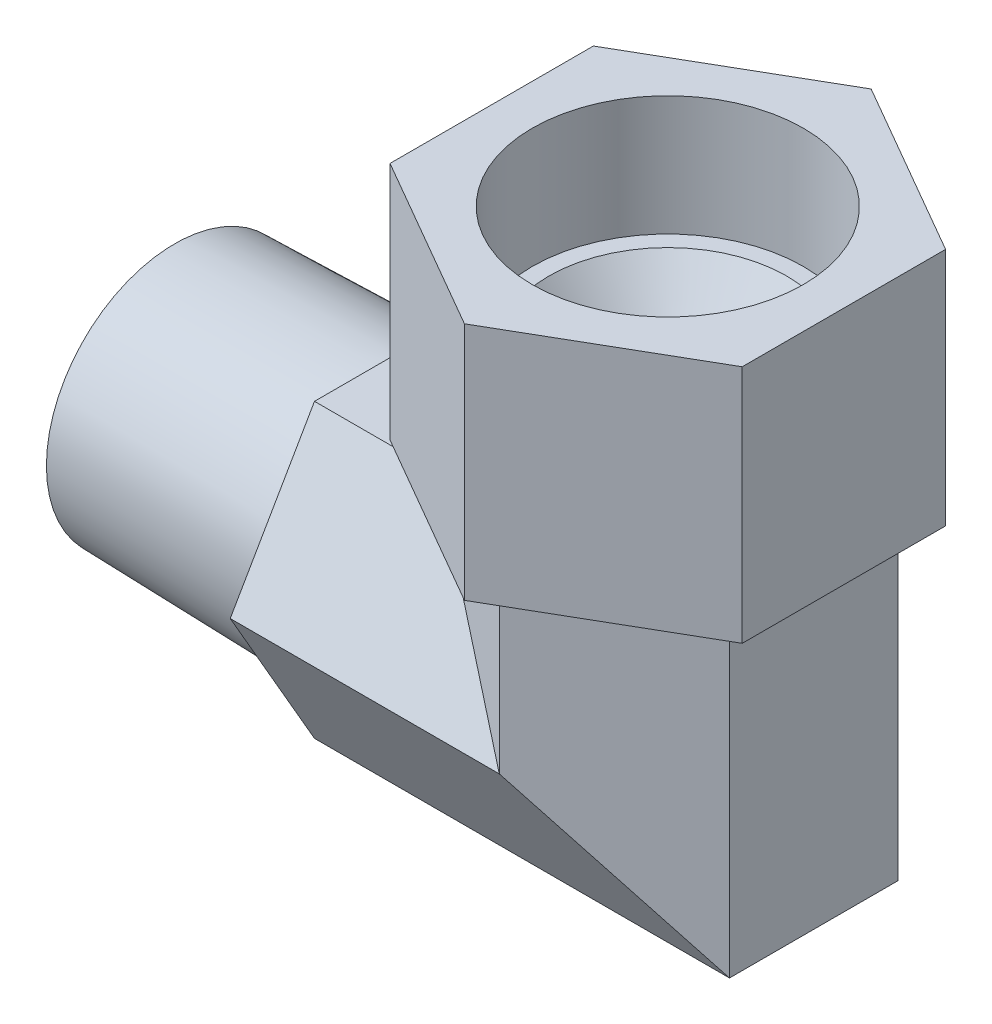
SolidWorks part; units mm, degrees
ref_plane "Front Plane" through (0, 0, 0) normal (0, 0, 1) x (1, 0, 0)
ref_plane "Top Plane" through (0, 0, 0) normal (0, 1, 0) x (1, 0, 0)
ref_plane "Right Plane" through (0, 0, 0) normal (1, 0, 0) x (0, 0, -1)
sketch "Sketch1" plane through (0, 0, 0) normal (0, 0, 1) x (1, 0, 0)
  line L0 (0, 0) -> (33.9096, 0) construction
  line L7 (0, 0) -> (44.45, 0)
  line L8 (44.45, 0) -> (44.45, 25.908)
  dimension "D1" = 44.45
  dimension "D2" = 25.908
ref_plane "Plane1" through (0, 0, 0) normal (1, 0, 0) x (0, 0, -1)
sketch "Sketch2" plane through (0, 0, 0) normal (1, 0, 0) x (0, 0, -1)
  line L0 (0, 0) -> (27.4531, 0) construction
  line L1 (7.5963, 13.1572) -> (-7.5963, 13.1572)
  line L2 (-7.5963, 13.1572) -> (-15.1926, 0)
  line L3 (-15.1926, 0) -> (-7.5963, -13.1572)
  line L4 (-7.5963, -13.1572) -> (7.5963, -13.1572)
  line L5 (7.5963, -13.1572) -> (15.1926, 0)
  line L6 (15.1926, 0) -> (7.5963, 13.1572)
  circle A0 centre (0, 0) radius 13.1572 construction
  dimension "D1" = 26.3144
sweep "Sweep1" add profiles "Sketch2" path "Sketch1"
sketch "Sketch3" plane through (0, 0, 0) normal (-1, 0, 0) x (0, 0, 1)
  circle A0 centre (0, 0) radius 9.1313
  dimension "D1" = 18.2626
extrude "Cut-Extrude1" cut sketch "Sketch3" against normal blind 52.1843
sketch "Sketch4" plane through (0, 25.908, 0) normal (0, 1, 0) x (1, 0, 0)
  line L0 (0, 0) -> (44.45, 0) construction
  line L1 (44.45, 15.1926) -> (44.45, -15.1926) construction
  line L2 (44.45, -15.1926) -> (31.2928, -7.5963) construction
  line L3 (0, -15.1926) -> (44.45, -15.1926) construction
  line L4 (57.6072, 0) -> (31.2928, 0) construction
  line L5 (57.6072, -7.5963) -> (57.6072, 7.5963) construction
  line L6 (31.2928, 7.5963) -> (31.2928, -7.5963) construction
  circle A0 centre (44.45, 0) radius 7.7343
  point P17 (0, 0)
  point P18 (0, 0)
  point P19 (0, 0)
  dimension "D1" = 15.4686
extrude "Cut-Extrude2" cut sketch "Sketch4" against normal blind 25.908
chamfer "Chamfer1" distance 3.9624 angle 37 1 edges at (36.7157, 25.908, 0) first distance on face at (36.7157, 25.908, 0)
sketch "Sketch5" plane through (0, 0, 0) normal (-1, 0, 0) x (0, 0, 1)
  line L6 (-7.5963, 13.1572) -> (-15.1926, 0)
  line L7 (-15.1926, 0) -> (-7.5963, -13.1572)
  line L8 (-7.5963, -13.1572) -> (7.5963, -13.1572)
  line L9 (7.5963, -13.1572) -> (15.1926, 0)
  line L10 (15.1926, 0) -> (7.5963, 13.1572)
  line L11 (7.5963, 13.1572) -> (-7.5963, 13.1572)
  line L12 (-7.5963, 13.1572) -> (-15.1926, 0)
  line L13 (-15.1926, 0) -> (-7.5963, -13.1572)
  line L14 (-7.5963, -13.1572) -> (7.5963, -13.1572)
  line L15 (7.5963, -13.1572) -> (15.1926, 0)
  line L16 (15.1926, 0) -> (7.5963, 13.1572)
  line L17 (7.5963, 13.1572) -> (-7.5963, 13.1572)
  circle A0 centre (0, 0) radius 11.5633
  dimension "D2" = 23.1267
  dimension "D1" = 0
extrude "Cut-Extrude3" cut sketch "Sketch5" against normal blind 20.1981 draft 1.47
sketch "Sketch6" plane through (0, 0, 0) normal (-1, 0, 0) x (0, 0, 1)
  line L0 (-15.1926, 0) -> (-7.5963, 13.1572) construction
  line L1 (-15.1926, 0) -> (-7.5963, 13.1572)
  line L2 (-7.5963, 13.1572) -> (7.5963, 13.1572) construction
  line L3 (-7.5963, 13.1572) -> (7.5963, 13.1572)
  line L4 (7.5963, 13.1572) -> (15.1926, 0) construction
  line L5 (7.5963, 13.1572) -> (15.1926, 0)
  line L6 (15.1926, 0) -> (7.5963, -13.1572) construction
  line L7 (15.1926, 0) -> (7.5963, -13.1572)
  line L8 (7.5963, -13.1572) -> (-7.5963, -13.1572) construction
  line L9 (7.5963, -13.1572) -> (-7.5963, -13.1572)
  line L10 (-7.5963, -13.1572) -> (-15.1926, 0) construction
  line L11 (-7.5963, -13.1572) -> (-15.1926, 0)
  circle A0 centre (0, 0) radius 12.0817 construction
  circle A1 centre (0, 0) radius 12.0817
extrude "Cut-Extrude4" cut sketch "Sketch6" against normal up to surface (20.1981 mm away) up to face at (20.1981, 0, 12.0817)
sketch "Sketch7" plane through (0, 25.908, 0) normal (0, 1, 0) x (1, 0, 0)
  line L0 (57.6072, 7.5963) -> (57.6072, -7.5963) construction
  line L1 (44.45, 18.3309) -> (28.575, 9.1654)
  line L2 (28.575, 9.1654) -> (28.575, -9.1654)
  line L3 (28.575, -9.1654) -> (44.45, -18.3309)
  line L4 (44.45, -18.3309) -> (60.325, -9.1654)
  line L5 (60.325, -9.1654) -> (60.325, 9.1654)
  line L6 (60.325, 9.1654) -> (44.45, 18.3309)
  circle A0 centre (44.45, 0) radius 15.875 construction
  circle A1 centre (44.45, 0) radius 12.2174
  dimension "D2" = 24.4348
  dimension "D1" = 31.75
extrude "Boss-Extrude1" add sketch "Sketch7" along normal mid plane 21.59
